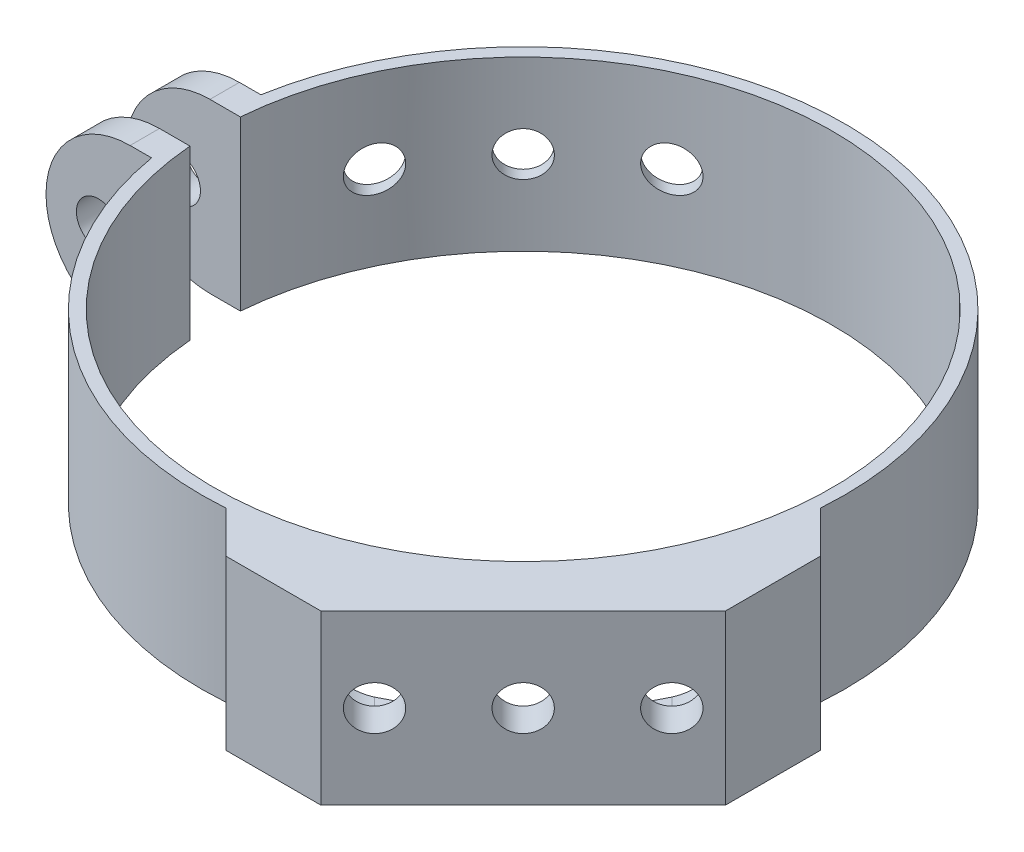
SolidWorks part; units mm, degrees
ref_plane "Front Plane" through (0, 0, 0) normal (0, 0, 1) x (1, 0, 0)
ref_plane "Top Plane" through (0, 0, 0) normal (0, 1, 0) x (1, 0, 0)
ref_plane "Right Plane" through (0, 0, 0) normal (1, 0, 0) x (0, 0, -1)
sketch "Sketch1" plane through (0, 0, 0) normal (0, 1, 0) x (1, 0, 0)
  line L0 (0, 0) -> (-38.25, 0) construction
  line L2 (-50.25, 6.5) -> (-37.6937, 6.5)
  line L3 (-50.25, 6.5) -> (-50.25, 3)
  line L4 (-50.25, 3) -> (-36.6273, 3)
  line L6 (-50.25, -6.5) -> (-50.25, -3)
  line L7 (-50.25, -3) -> (-36.6273, -3)
  line L8 (-50.25, -6.5) -> (-37.6937, -6.5)
  line L9 (38.1479, -2.7926) -> (2.7926, -38.1479)
  line L10 (38.1479, -2.7926) -> (48.7545, -13.3992)
  line L11 (2.7926, -38.1479) -> (13.3992, -48.7545)
  line L12 (48.7545, -13.3992) -> (13.3992, -48.7545)
  arc A0 (-36.6273, -3) -> (-36.6273, 3) centre (0, 0) ccw
  arc A1 (-37.6937, -6.5) -> (-37.6937, 6.5) centre (0, 0) ccw
  circle A2 centre (0, 0) radius 38.25 construction
  circle A3 centre (0, 0) radius 36.75 construction
  point P4 (0, 0)
  point P10 (33.8966, 17.7224)
  dimension "D1" = 73.5
  dimension "D3" = 3.5
  dimension "D4" = 3
  dimension "D5" = 12
  dimension "D6" = 38.25
  dimension "D7" = 90
  dimension "D8" = 135
  dimension "D9" = 50
  dimension "D10" = 15
  dimension "D2" = 1.5
extrude "Boss-Extrude1" add sketch "Sketch1" along normal mid plane 20 contours L9 A1 L2 L3 L4 A0 | A1 L11 L12 L10 | L8 A1 L9 A0 L7 L6 | L9 A1 A0 region at (-43.9718, 0, -5.5173) region at (26.6933, 0, 26.6933) region at (27.7239, 0, 27.7239) region at (-23.1559, 0, 29.6226)
sketch "Sketch2" plane through (0, 0, 6.5) normal (0, 0, 1) x (1, 0, 0)
  line L0 (-43.9718, 10) -> (-43.9718, -10) construction
  line L1 (-50.25, 10) -> (-37.6937, 10) construction
  line L2 (-50.25, -10) -> (-37.6937, -10) construction
  line L3 (-50.25, 10) -> (-50.25, -10) construction
  circle A0 centre (-44.0082, 0) radius 2.625
  dimension "D1" = 5.25
  dimension "D2" = 6.2418
extrude "Cut-Extrude1" cut sketch "Sketch2" against normal through all
sketch "Sketch3" plane through (31.0769, 0, 31.0769) normal (0.7071, 0, 0.7071) x (0.7071, 0, -0.7071)
  line L0 (0, 0) -> (-25, 0) construction
  line L1 (-25, 10) -> (-25, -10) construction
  line L2 (0, 0) -> (25, 0) construction
  line L3 (25, 10) -> (25, -10) construction
  circle A0 centre (0, 0) radius 2.625
  circle A1 centre (-12.5, 0) radius 2.625
  circle A2 centre (12.5, 0) radius 2.625
  point P7 (12.5, 0)
  dimension "D1" = 5.25
extrude "Cut-Extrude2" cut sketch "Sketch3" against normal through all
ref_plane "Plane1" through (20.4703, 0, 20.4703) normal (0.7071, 0, 0.7071) x (0.7071, 0, -0.7071)
sketch "Sketch6" plane through (20.4703, 0, 20.4703) normal (0.7071, 0, 0.7071) x (0.7071, 0, -0.7071)
  line L0 (12.5, 0) -> (-12.5, 0) construction
  line L1 (12.5, -5.5) -> (-12.5, -5.5)
  line L2 (12.5, 5.5) -> (-12.5, 5.5)
  arc A0 (12.5, -5.5) -> (12.5, 5.5) centre (12.5, 0) ccw
  arc A1 (-12.5, 5.5) -> (-12.5, -5.5) centre (-12.5, 0) ccw
  circle A2 centre (12.5, 0) radius 2.625 construction
  circle A3 centre (12.5, 0) radius 2.625 construction
  point P2 (0, 0)
  point P11 (0, 0)
  point P12 (12.5, 0)
  dimension "D1" = 5.5
extrude "Cut-Extrude3" cut sketch "Sketch6" along normal blind 11
fillet "Fillet1" radius 10 4 edges at (-50.25, 10, 4.75) (-50.25, -10, 4.75) (-50.25, -10, -4.75) (-50.25, 10, -4.75)
chamfer "Chamfer1" distance 8 angle 45 2 edges at (48.7545, 0, 13.3992) (13.3992, 0, 48.7545)
